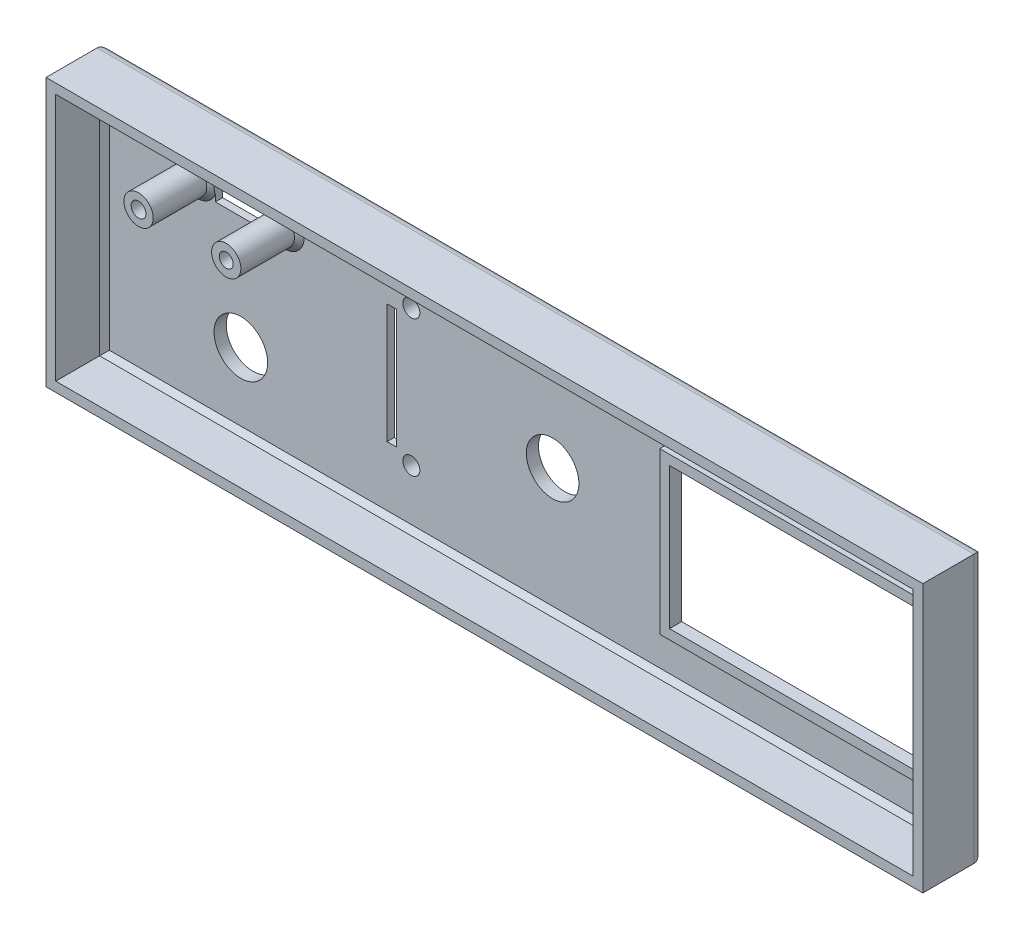
SolidWorks part; units mm, degrees
ref_plane "Спереди" through (0, 0, 0) normal (0, 0, 1) x (1, 0, 0)
ref_plane "Сверху" through (0, 0, 0) normal (0, 1, 0) x (1, 0, 0)
ref_plane "Справа" through (0, 0, 0) normal (1, 0, 0) x (0, 0, -1)
sketch "Эскиз1" plane through (0, 0, 0) normal (0, 0, 1) x (1, 0, 0)
  line L1 (-88, 25.5) -> (88, 25.5)
  line L2 (-88, 25.5) -> (-88, -25.5)
  line L3 (-88, -25.5) -> (88, -25.5)
  line L4 (88, 25.5) -> (88, -25.5)
  line L5 (-88, 25.5) -> (88, -25.5) construction
  line L6 (-88, -25.5) -> (88, 25.5) construction
  point P0 (0, 0)
  dimension "D1" = 176
  dimension "D2" = 51
extrude "Вытянуть-Тонкостенный1" add sketch "Эскиз1" along normal blind 10 thin thin type one direction wall 2
sketch "Эскиз4" plane through (0, 0, 0) normal (0, 0, -1) x (-1, 0, 0)
  line L1 (90, -27.5) -> (-90, -27.5)
  line L2 (90, -27.5) -> (90, 27.5)
  line L3 (90, 27.5) -> (-90, 27.5)
  line L4 (-90, -27.5) -> (-90, 27.5)
extrude "Бобышка-Вытянуть2" add sketch "Эскиз4" along normal blind 2.5
sketch "Эскиз5" plane through (0, 0, -2.5) normal (0, 0, -1) x (-1, 0, 0)
  line L0 (-99.6943, 0) -> (99.6943, 0)
  line L4 (54.75, 18.25) -> (65.25, 18.25)
  line L5 (54.75, 18.25) -> (54.75, 12.75)
  line L6 (54.75, 12.75) -> (65.25, 12.75)
  line L7 (65.25, 18.25) -> (65.25, 12.75)
  line L8 (54.75, 18.25) -> (65.25, 12.75) construction
  line L9 (54.75, 12.75) -> (65.25, 18.25) construction
  point P4 (0, 0)
  point P10 (60, 15.5)
  point P15 (-91.9027, 13.9127)
extrude "Вырез-Вытянуть1" cut sketch "Эскиз5" against normal blind 2.5 contours L7 L4 L5 L6 region at (-60, 15.5, -2.5)
sketch "Эскиз7" plane through (0, 0, 0) normal (0, 0, 1) x (1, 0, 0)
  line L0 (-69, 15.5) -> (-51, 15.5) construction
  line L1 (-60, 12.75) -> (-60, 38.329) construction
  line L2 (-54.75, 12.75) -> (-65.25, 12.75) construction
  line L3 (-69, 15.5) -> (-69, 33.9874) construction
  line L6 (-51, 15.5) -> (-51, 34.7395) construction
  circle A0 centre (-51, 15.5) radius 3
  circle A1 centre (-69, 15.5) radius 3
  dimension "D1" = 9
  dimension "D2" = 9
extrude "Бобышка-Вытянуть3" add sketch "Эскиз7" along normal blind 12
sketch "Эскиз8" plane through (0, 0, 12) normal (0, 0, 1) x (1, 0, 0)
  line L0 (-72, 15.5) -> (-44.9054, 15.5) construction
  line L2 (-51, 18.5) -> (-51, 7.9878) construction
  line L4 (-69.1366, 7.9878) -> (-69.1366, 21.896) construction
  circle A0 centre (-69, 15.5) radius 3 construction
  circle A1 centre (-69, 15.5) radius 3 construction
  circle A2 centre (-51, 15.5) radius 3 construction
  circle A3 centre (-51, 15.5) radius 3 construction
  circle A4 centre (-69, 15.5) radius 1.5173
  circle A5 centre (-51, 15.5) radius 1.4341
extrude "Вырез-Вытянуть2" cut sketch "Эскиз8" against normal blind 8
sketch "Эскиз9" plane through (0, 0, -2.5) normal (0, 0, -1) x (-1, 0, 0)
  line L0 (60, 18.25) -> (60, -39.25) construction
  line L1 (54.75, 18.25) -> (65.25, 18.25) construction
  line L2 (-107.013, -12.5) -> (126.1089, -12.5) construction
  line L3 (126.1089, -12.5) -> (126.1089, 17.3777) construction
  circle A0 centre (60, -10.5) radius 5.5
  dimension "D2" = 17
  dimension "D1" = 15
extrude "Вырез-Вытянуть3" cut sketch "Эскиз9" against normal blind 8
sketch "Эскиз10" plane through (0, 0, -2.5) normal (0, 0, -1) x (-1, 0, 0)
  line L0 (25, 34.8185) -> (25, -39.1882) construction
  line L1 (-90, 0) -> (112.0403, 0) construction
  line L2 (-90, 27.5) -> (-90, -27.5) construction
  line L3 (7.1273, 14) -> (41.6077, 14) construction
  line L4 (7.1273, -14) -> (41.6077, -14) construction
  circle A0 centre (25, 14) radius 1.75
  circle A1 centre (25, -14) radius 1.75
  dimension "D1" = 65
  dimension "D2" = 14
  dimension "D3" = 14
extrude "Вырез-Вытянуть4" cut sketch "Эскиз10" against normal blind 8
sketch "Эскиз12" plane through (0, 0, -2.5) normal (0, 0, -1) x (-1, 0, 0)
  line L0 (0, 0) -> (84.374, 0) construction
  line L1 (25, 14) -> (25, 27.5) construction
  line L2 (90, 27.5) -> (-90, 27.5) construction
  line L3 (29, 0) -> (29, 27.5) construction
  line L4 (25, 12.25) -> (33.1859, 12.25) construction
  line L5 (25, -12.25) -> (33.4448, -12.25) construction
  line L7 (28, 12.25) -> (30, 12.25)
  line L8 (28, 12.25) -> (28, -12.25)
  line L9 (28, -12.25) -> (30, -12.25)
  line L10 (30, 12.25) -> (30, -12.25)
  line L11 (28, 12.25) -> (30, -12.25) construction
  line L12 (28, -12.25) -> (30, 12.25) construction
  circle A0 centre (25, 14) radius 1.75 construction
  circle A1 centre (25, -14) radius 1.75 construction
  dimension "D1" = 4
  dimension "D2" = 2
extrude "Вырез-Вытянуть5" cut sketch "Эскиз12" against normal blind 8
sketch "Эскиз13" plane through (0, 0, -2.5) normal (0, 0, -1) x (-1, 0, 0)
  line L0 (-4, -33.8219) -> (-4, 43.2368) construction
  line L1 (-90, 0) -> (16.8794, 0) construction
  line L2 (-90, 27.5) -> (-90, -27.5) construction
  circle A0 centre (-4, 0) radius 5.4
  dimension "D1" = 4
extrude "Вырез-Вытянуть6" cut sketch "Эскиз13" against normal blind 8
sketch "Эскиз15" plane through (0, 0, -2.5) normal (0, 0, -1) x (-1, 0, 0)
  line L0 (0, 0) -> (-107.8488, 0) construction
  line L1 (-80, 31.1202) -> (-80, -32.9625) construction
  line L2 (-94.8238, 14.5) -> (-23.9681, 14.5) construction
  line L3 (-92.8701, -14.5) -> (-23.9681, -14.5) construction
  line L4 (-26, 31.1202) -> (-26, -20.3283) construction
  line L6 (-80, 14.5) -> (-30, 14.5)
  line L7 (-80, 14.5) -> (-80, -14.5)
  line L8 (-80, -14.5) -> (-30, -14.5)
  line L9 (-30, 14.5) -> (-30, -14.5)
  dimension "D1" = 10
  dimension "D2" = 14.5
  dimension "D3" = 14.5
  dimension "D4" = 54
extrude "Вырез-Вытянуть7" cut sketch "Эскиз15" against normal blind 8
sketch "Эскиз16" plane through (0, 0, 0) normal (0, 0, 1) x (1, 0, 0)
  line L1 (30, 14.5) -> (80, 14.5)
  line L2 (30, 14.5) -> (30, -14.5)
  line L3 (30, -14.5) -> (80, -14.5)
  line L4 (80, 14.5) -> (80, -14.5)
extrude "Вытянуть-Тонкостенный2" add sketch "Эскиз16" along normal blind 2 thin thin type one direction wall 2
chamfer "Фаска1" distance 2 angle 45 4 edges at (55, -14.5, -2.5) (30, 0, -2.5) (55, 14.5, -2.5) (80, 0, -2.5)
chamfer "Фаска2" distance 1 angle 45 4 edges at (-29, -12.25, -2.5) (-28, 0, -2.5) (-29, 12.25, -2.5) (-30, 0, -2.5)
chamfer "Фаска3" distance 1 angle 45 4 edges at (-65.25, 15.5, -2.5) (-60, 12.75, -2.5) (-54.75, 15.5, -2.5) (-60, 18.25, -2.5)
chamfer "Фаска4" distance 1 angle 45 2 edges at (-54, 15.5, 0) (-72, 15.5, 0)
chamfer "Фаска5" distance 1 angle 45 4 edges at (-88, 0, 0) (0, 25.5, 0) (88, 0, 0) (0, -25.5, 0)
fillet "Скругление1" radius 2 4 edges at (-90, 0, -2.5) (0, -27.5, -2.5) (0, 27.5, -2.5) (90, 0, -2.5)
equation "\"D2@Эскиз7\"=\"D1@Эскиз7\""
